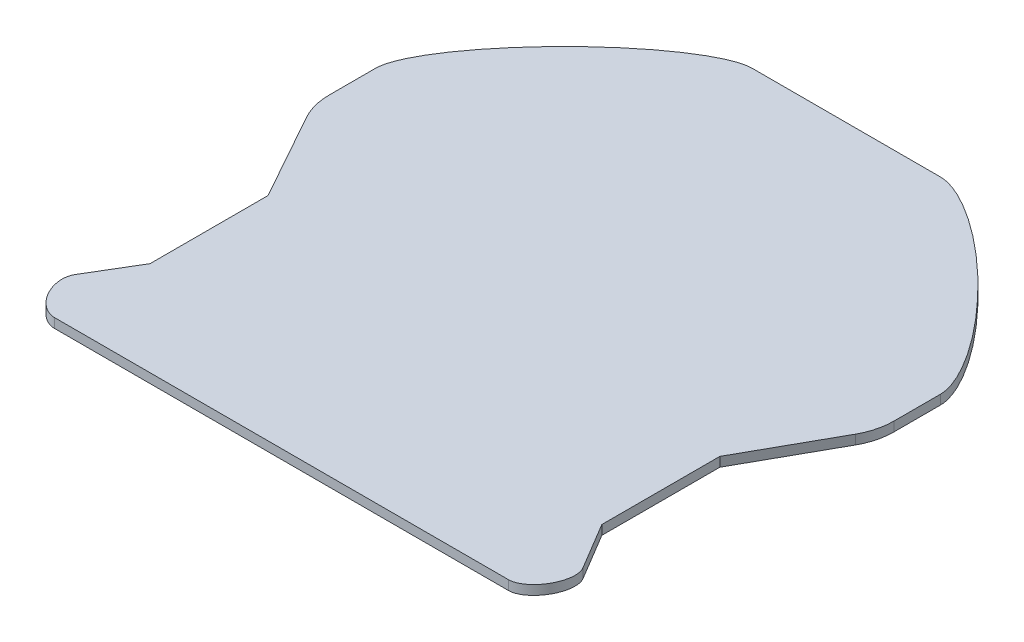
SolidWorks part; units mm, degrees
ref_plane "Front Plane" through (0, 0, 0) normal (0, 0, 1) x (1, 0, 0)
ref_plane "Top Plane" through (0, 0, 0) normal (0, 1, 0) x (1, 0, 0)
ref_plane "Right Plane" through (0, 0, 0) normal (1, 0, 0) x (0, 0, -1)
sketch "Sketch1" plane through (0, 0, 0) normal (0, 1, 0) x (1, 0, 0)
  line L0 (-90, 180) -> (-90, 0) construction
  line L1 (-180, 180) -> (0, 180)
  line L2 (-180, 180) -> (-180, 0)
  line L3 (-180, 0) -> (0, 0)
  line L4 (0, 180) -> (0, 0)
  line L5 (-180, 90) -> (0, 90) construction
  line L6 (-180, 30) -> (0, 30)
  line L7 (-130, 30) -> (-50, 30)
  line L8 (-130, 30) -> (-130, -30)
  line L9 (-130, -30) -> (-50, -30)
  line L10 (-50, 30) -> (-50, -30)
  line L11 (-130, 30) -> (-50, -30) construction
  line L12 (-130, -30) -> (-50, 30) construction
  dimension "D1" = 180
  dimension "D2" = 180
  dimension "D3" = 60
  dimension "D4" = 80
extrude "Boss-Extrude1" add sketch "Sketch1" along normal blind 3 contours L10 L3 L8 L9 | L2 L6 L4 L1 | L6 L10 L3 L4 | L8 L6 L2 L3 | L10 L6 L8 L3 region at (-90, 0, -105) region at (-155, 0, -15) region at (-25, 0, -15) region at (-90, 0, -15) region at (-90, 0, 15)
sketch "Sketch2" plane through (0, 3, 0) normal (0, 1, 0) x (1, 0, 0)
  line L0 (-180, 30) -> (0, 30)
  line L1 (-180, 180) -> (-180, 0) construction
  line L2 (0, 180) -> (0, 0) construction
  line L3 (-180, 180) -> (0, 180) construction
  line L4 (-90, 180) -> (-90, -30) construction
  line L5 (-130, -30) -> (-50, -30) construction
  dimension "D1" = 150
sketch "Sketch3" plane through (0, 3, 0) normal (0, 1, 0) x (1, 0, 0)
  line L0 (-180, 122) -> (0, 122)
  line L1 (-180, 180) -> (-180, 0) construction
  line L2 (0, 180) -> (0, 0) construction
  line L3 (-180, 30) -> (0, 30) construction
  dimension "D1" = 92
sketch "Sketch5" plane through (0, 3, 0) normal (0, 1, 0) x (1, 0, 0)
  line L0 (-114, 180) -> (-114, -30)
  line L1 (-180, 180) -> (0, 180) construction
  line L2 (-130, -30) -> (-50, -30) construction
  line L3 (-90, 180) -> (-90, -30) construction
  dimension "D1" = 24
fillet "Fillet1" radius 60 2 edges at (0, 1.5, -180) (-180, 1.5, -180) conic rho 0.2
sketch "Sketch6" plane through (0, 3, 0) normal (0, 1, 0) x (1, 0, 0)
  line L0 (-50, 0) -> (-130, 0)
  line L1 (-130, 0) -> (-130, -30)
  line L2 (-130, -30) -> (-50, -30)
  line L3 (-50, -30) -> (-50, 0)
  line L4 (-180, 0) -> (-162, 30.1113)
  line L5 (-162, 30.1113) -> (-162, 67.7113)
  line L6 (-162, 67.7113) -> (-180, 100)
  line L7 (-180, 120) -> (-180, 0) construction
  line L8 (-90, 180) -> (-90, -30) construction
  line L10 (-90, 180) -> (-90, 0) construction
  line L11 (0, 0) -> (-18, 30.1113)
  line L12 (-18, 30.1113) -> (-18, 67.7113)
  line L13 (-18, 67.7113) -> (0, 100)
  line M3 (0, 0) -> (0, 120)
  line M7 (-180, 120) -> (-180, 0)
  line M9 (-130, 0) -> (-130, -30)
  line M10 (-130, -30) -> (-50, -30)
  line M11 (-50, -30) -> (-50, 0)
  dimension "D1" = 37.6
  dimension "D2" = 72
  dimension "D3" = 100
extrude "Cut-Extrude1" cut sketch "Sketch6" against normal blind 10 contours L0 M11 M9 M10 | L5 L6 L4 M7 | L13 L12 L11 M3 region at (-90, 3, 15) region at (-172.3605, 3, -49.5379) region at (-7.6395, 3, -49.5379)
fillet "Fillet2" radius 10 2 edges at (-180, 1.5, 0) (0, 1.5, 0) conic rho 0.25
fillet "Fillet3" radius 20 2 edges at (-180, 1.5, -100) (0, 1.5, -100)
